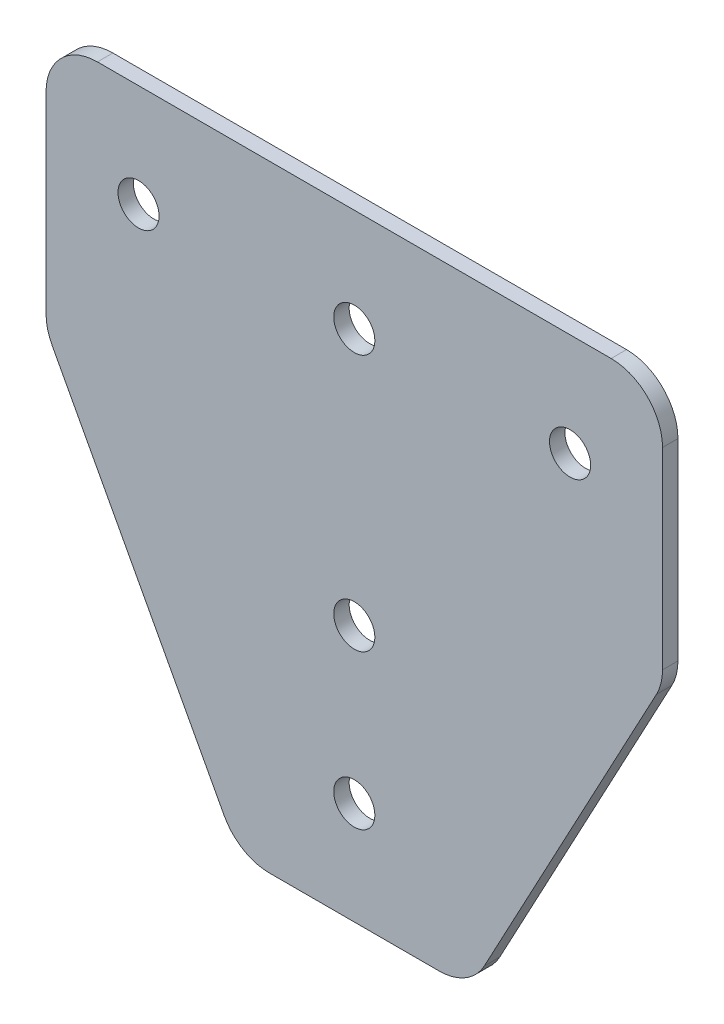
SolidWorks part; units mm, degrees
ref_plane "Ön Düzlem" through (0, 0, 0) normal (0, 0, 1) x (1, 0, 0)
ref_plane "Üst Düzlem" through (0, 0, 0) normal (0, 1, 0) x (1, 0, 0)
ref_plane "Sağ Düzlem" through (0, 0, 0) normal (1, 0, 0) x (0, 0, -1)
sketch "Sketch1" plane through (0, 0, 0) normal (0, 0, 1) x (1, 0, 0)
  line L0 (-60, 60) -> (-60, 10)
  line L1 (-60, 10) -> (-22.5, -60)
  line L2 (-60, 60) -> (60, 60)
  line L3 (-22.5, -60) -> (22.5, -60)
  line L4 (0, -60) -> (0, 60) construction
  line L5 (60, 60) -> (60, 10)
  line L6 (60, 10) -> (22.5, -60)
  circle A0 centre (-42, 40) radius 4
  circle A1 centre (0, -40) radius 4
  circle A2 centre (0, -10) radius 4
  circle A3 centre (0, 40) radius 4
  circle A4 centre (42, 40) radius 4
  dimension "D5" = 8
  dimension "D1" = 60
  dimension "D2" = 22.5
  dimension "D3" = 50
  dimension "D4" = 120
  dimension "D6" = 20
  dimension "D7" = 18
  dimension "D8" = 20
  dimension "D9" = 30
extrude "Boss-Extrude1" add sketch "Sketch1" along normal blind 3
fillet "Fillet1" radius 10 6 edges at (60, 60, 1.5) (60, 10, 1.5) (22.5, -60, 1.5) (-22.5, -60, 1.5) (-60, 10, 1.5) (-60, 60, 1.5)
ref_axis "Axis1" through (0, -40, 3) along (0, 0, -1)
ref_axis "Axis2" through (0, 40, 3) along (0, 0, -1)
ref_axis "Axis3" through (42, 40, 3) along (0, 0, -1)
